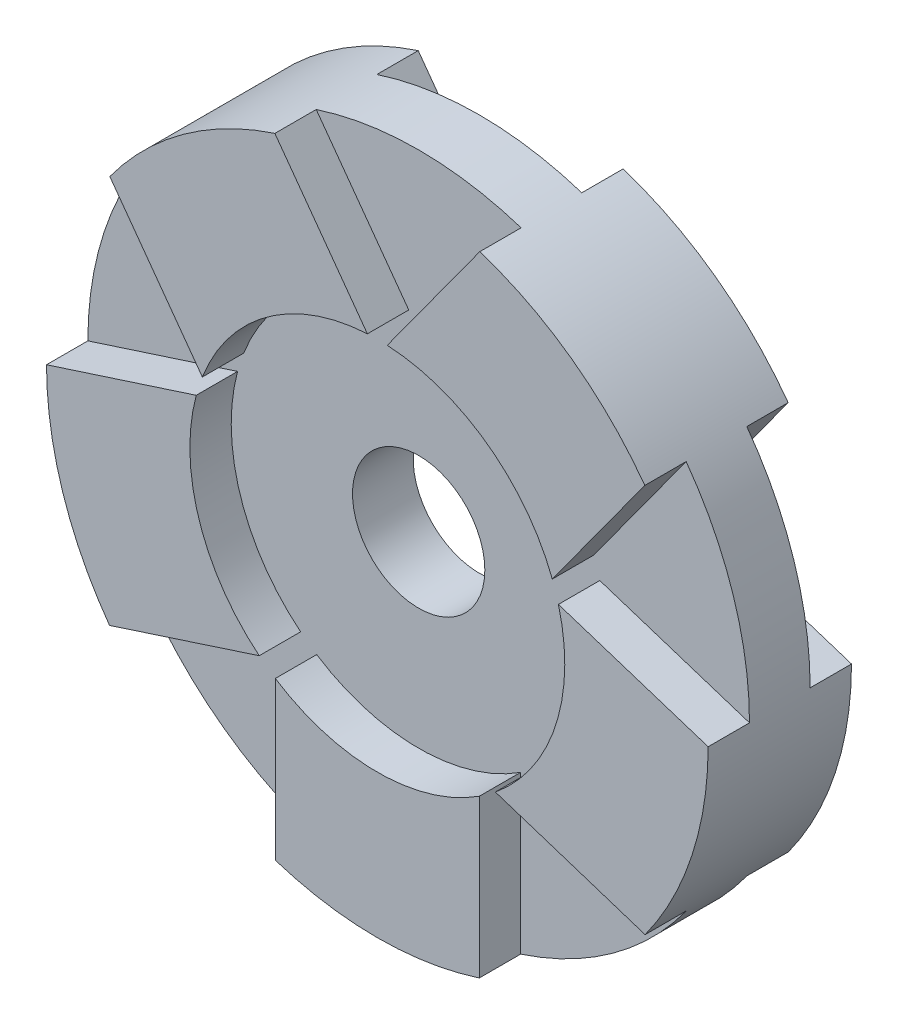
SolidWorks part; units mm, degrees
ref_plane "Plan de face" through (0, 0, 0) normal (0, 0, 1) x (1, 0, 0)
ref_plane "Plan de dessus" through (0, 0, 0) normal (0, 1, 0) x (1, 0, 0)
ref_plane "Plan de droite" through (0, 0, 0) normal (1, 0, 0) x (0, 0, -1)
sketch "Esquisse1" plane through (0, 0, 0) normal (0, 0, 1) x (1, 0, 0)
  circle A0 centre (0, 0) radius 30
  circle A1 centre (0, 0) radius 6
  dimension "D1" = 60
  dimension "D2" = 12
extrude "Boss.-Extru.1" add sketch "Esquisse1" along normal blind 6.5 and the other way blind 6.5
sketch "Esquisse3" plane through (0, 0, 6.5) normal (0, 0, 1) x (1, 0, 0)
  line L0 (0, -30) -> (0, 30) construction
  line L1 (0, -30) -> (0, -17)
  line L2 (-9.25, -30.9509) -> (9.25, -30.9509)
  line L3 (-9.25, -31.0329) -> (-9.25, -14.2632) construction
  line L4 (9.25, -31.0329) -> (9.25, -14.2632) construction
  line L5 (-32.2944, -0.7671) -> (-26.5776, -18.3616)
  line L6 (-32.3724, -0.7924) -> (-16.4235, 4.3897) construction
  line L7 (-26.6556, -18.387) -> (-10.7067, -13.2048) construction
  line L8 (-10.7091, 30.4768) -> (-25.6759, 19.6028)
  line L9 (-10.7572, 30.5431) -> (-0.9003, 16.9761) construction
  line L10 (-25.7241, 19.6691) -> (-15.8671, 6.1021) construction
  line L11 (25.6759, 19.6028) -> (10.7091, 30.4768)
  line L12 (25.7241, 19.6691) -> (15.8671, 6.1021) construction
  line L13 (10.7572, 30.5431) -> (0.9003, 16.9761) construction
  line L14 (26.5776, -18.3616) -> (32.2944, -0.7671)
  line L15 (26.6556, -18.387) -> (10.7067, -13.2048) construction
  line L16 (32.3724, -0.7924) -> (16.4235, 4.3897) construction
  line L17 (-10.7067, -13.2048) -> (-24.2832, -17.6161)
  line L18 (-9.25, -14.2632) -> (-9.25, -28.5384)
  line L19 (9.25, -14.2632) -> (9.25, -28.5384)
  line L20 (10.7067, -13.2048) -> (24.2832, -17.6161)
  line L21 (16.4235, 4.3897) -> (30, 0)
  line L22 (15.8671, 6.1021) -> (24.2578, 17.651)
  line L23 (0.9003, 16.9761) -> (9.291, 28.525)
  line L24 (-0.9003, 16.9761) -> (-9.291, 28.525)
  line L25 (-15.8671, 6.1021) -> (-24.2578, 17.651)
  line L26 (-16.4235, 4.3897) -> (-30, 0)
  circle A0 centre (0, 0) radius 30 construction
  circle A1 centre (0, 0) radius 17
  circle A2 centre (0, 0) radius 30
  point P12 (0, -30.9509)
  circle M2 centre (0, 0) radius 30
  circle M3 centre (0, 0) radius 6
  dimension "D1" = 13
  dimension "D2" = 18.5
  dimension "D3" = 5
extrude "Enlèv. mat.-Extru.1" cut sketch "Esquisse3" against normal blind 3.75 contours A1 L0 M3 | L0 A1 M3 | A1 L25 L26 M2 | A1 L17 L18 M2 | A1 L19 L20 M2 | A1 L21 L22 M2 | A1 L23 L24 M2 region at (-4.6868, -15.8404, 6.5) region at (-14.6842, -20.2111, 6.5) region at (14.6842, -20.2111, 6.5) region at (-23.7577, 7.7267, 6.5) region at (23.7577, 7.7267, 6.5) region at (0, 24.9823, 6.5)
mirror "Symétrie1" about plane through (0, 0, 0) normal (0, 0, 1) of "Enlèv. mat.-Extru.1"
